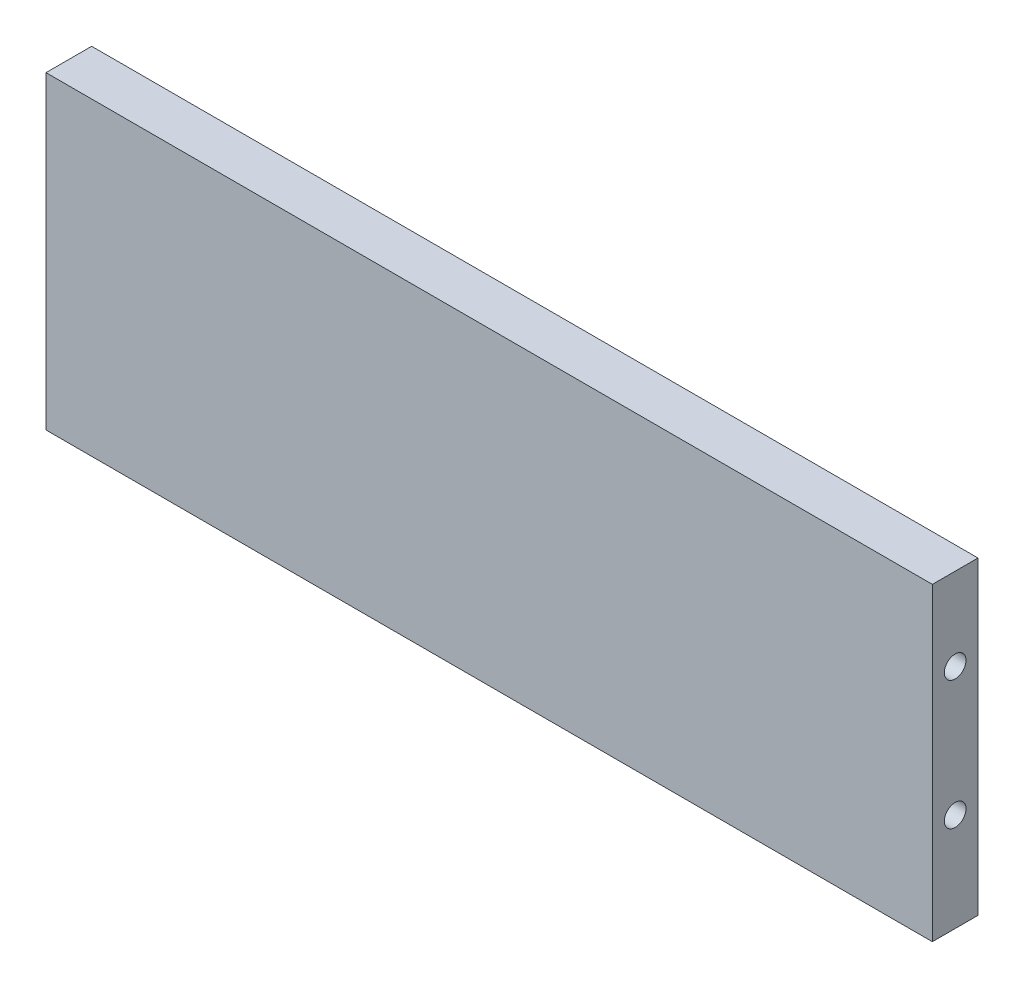
SolidWorks part; units mm, degrees
ref_plane "Front Plane" through (0, 0, 0) normal (0, 0, 1) x (1, 0, 0)
ref_plane "Top Plane" through (0, 0, 0) normal (0, 1, 0) x (1, 0, 0)
ref_plane "Right Plane" through (0, 0, 0) normal (1, 0, 0) x (0, 0, -1)
sketch "Sketch2" plane through (0, 0, 0) normal (0, 0, 1) x (1, 0, 0)
  line L1 (-46.228, -16.1417) -> (46.228, -16.1417)
  line L2 (-46.228, -16.1417) -> (-46.228, 16.1417)
  line L3 (-46.228, 16.1417) -> (46.228, 16.1417)
  line L4 (46.228, -16.1417) -> (46.228, 16.1417)
  line L5 (-46.228, -16.1417) -> (46.228, 16.1417) construction
  line L6 (-46.228, 16.1417) -> (46.228, -16.1417) construction
  point P0 (0, 0)
  dimension "D1" = 92.456
  dimension "D2" = 32.2834
extrude "Boss-Extrude1" add sketch "Sketch2" along normal blind 4.7625
sketch "Sketch3" plane through (-46.228, 0, 0) normal (-1, 0, 0) x (0, 0, 1)
  circle A0 centre (2.3812, 7.5311) radius 1.1303
  circle A1 centre (2.3812, -5.8801) radius 1.1303
  circle A2 centre (2.3812, -5.8801) radius 1.524 construction
  circle A3 centre (2.3812, 7.5311) radius 1.524 construction
  dimension "D1" = 2.2606
extrude "Cut-Extrude1" cut sketch "Sketch3" against normal through all
sketch "Sketch4" plane through (0, -16.1417, 0) normal (0, -1, 0) x (1, 0, 0)
  line L1 (-46.228, 4.7625) -> (-46.228, 0) construction
  line L2 (46.228, 4.7625) -> (46.228, 0) construction
  circle A0 centre (-20.828, 2.3813) radius 1.1303
  circle A1 centre (20.828, 2.3813) radius 1.1303
  point P9 (46.228, 2.3813)
  dimension "D1" = 2.2606
  dimension "D2" = 25.4
  dimension "D3" = 25.4
extrude "Cut-Extrude2" cut sketch "Sketch4" against normal blind 19.05
